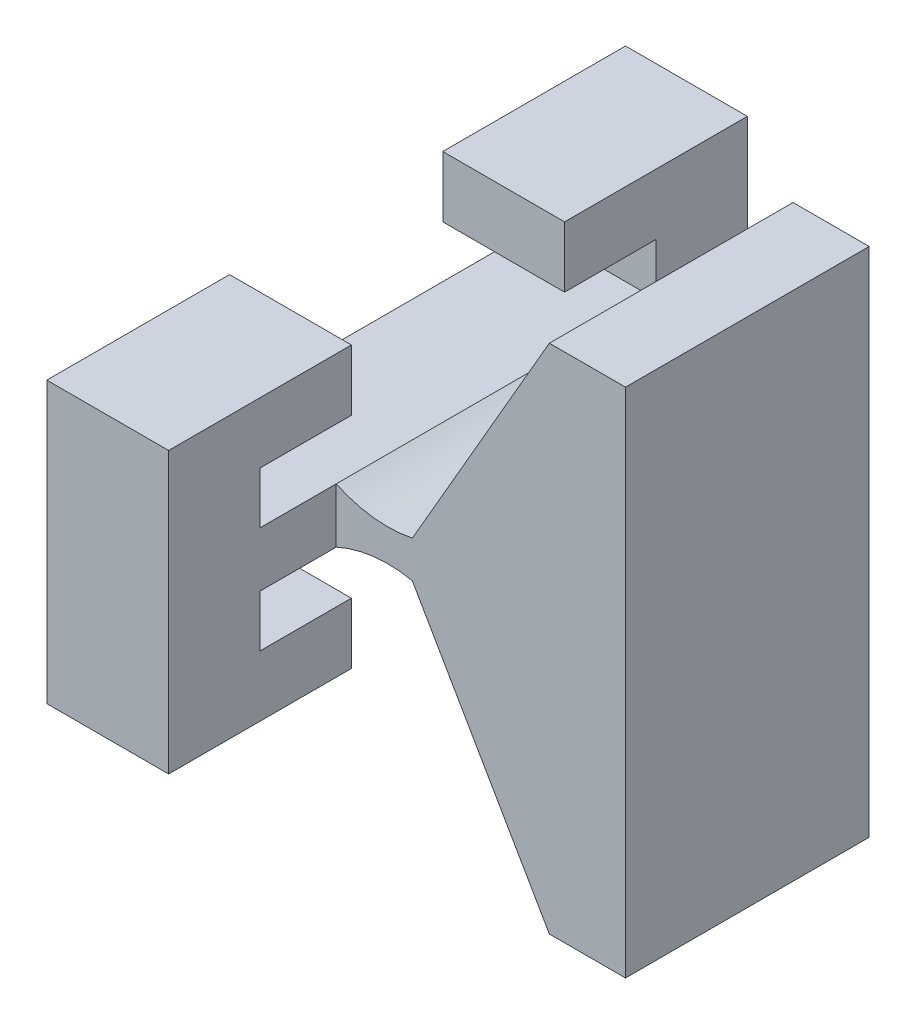
SolidWorks part; units mm, degrees
material "Резина"
ref_plane "Plane1" through (0, 0, 0) normal (0, 0, 1) x (1, 0, 0)
ref_plane "Plane2" through (0, 0, 0) normal (0, 1, 0) x (1, 0, 0)
ref_plane "Plane3" through (0, 0, 0) normal (1, 0, 0) x (0, 0, -1)
sketch "Эскиз2" plane through (0, 0, 0) normal (0, 0, 1) x (1, 0, 0)
  line L0 (0, 0) -> (0, 0.9)
  line L1 (0, 0.9) -> (4, 0.9)
  line L2 (0, 0) -> (34.0426, 0) construction
  line L3 (13.5, 8.4) -> (13.5, -8.4)
  line L4 (11, 8.4) -> (6.5, 0.6058)
  line L5 (11, 8.4) -> (13.5, 8.4)
  line L6 (0, 0) -> (0, -0.9)
  line L7 (0, -0.9) -> (4, -0.9)
  line L8 (11, -8.4) -> (6.5, -0.6058)
  line L9 (11, -8.4) -> (13.5, -8.4)
  arc A0 (6.5, 0.6058) -> (4, 0.9) centre (5.6938, 4.5237) cw
  arc A1 (6.5, -0.6058) -> (4, -0.9) centre (5.6938, -4.5237) ccw
  point P18 (13.5, 0)
  dimension "D1" = 4
  dimension "D2" = 4
  dimension "D3" = 16.8
  dimension "D4" = 2.5
  dimension "D5" = 9
  dimension "D6" = 60
  dimension "D7" = 7
  dimension "D8" = 1.8
  dimension "D9" = 9.5
extrude "Бобышка-Вытянуть1" add sketch "Эскиз2" along normal mid plane 8
sketch "Эскиз3" plane through (0, 0, -4) normal (0, 0, -1) x (-1, 0, 0)
  line L1 (0, -0.9) -> (-4, -0.9)
  line L2 (0, -0.9) -> (0, 0.9)
  line L3 (0, 0.9) -> (-4, 0.9)
  line L4 (-4, -0.9) -> (-4, 0.9)
extrude "Бобышка-Вытянуть2" add sketch "Эскиз3" along normal blind 5.5
mirror "Зеркальное отражение1" about plane through (0, 0, 0) normal (0, 0, 1) of "Бобышка-Вытянуть2"
sketch "Эскиз5" plane through (0, 0.9, 0) normal (0, 1, 0) x (1, 0, 0)
  line L0 (0, 9.5) -> (4, 9.5)
  line L1 (0, 9.5) -> (0, 6.5)
  line L2 (4, 9.5) -> (4, 6.5)
  line L3 (0, 6.5) -> (4, 6.5)
  dimension "D1" = 3
extrude "Бобышка-Вытянуть3" add sketch "Эскиз5" along normal blind 3.7
mirror "Зеркальное отражение2" about plane through (0, 0, 0) normal (0, 0, 1) of "Бобышка-Вытянуть3"
mirror "Зеркальное отражение3" about plane through (0, 0, 0) normal (0, 1, 0) of "Зеркальное отражение2"
sketch "Эскиз7" plane through (0, 0, 6.5) normal (0, 0, -1) x (-1, 0, 0)
  line L0 (0, -4.6) -> (0, 4.6) construction
  line L1 (-4, 4.6) -> (0, 4.6)
  line L2 (-4, 4.6) -> (-4, 2.6)
  line L3 (-4, 2.6) -> (0, 2.6)
  line L4 (0, 4.6) -> (0, 2.6)
  dimension "D1" = 2
extrude "Бобышка-Вытянуть4" add sketch "Эскиз7" along normal blind 3
mirror "Зеркальное отражение4" about plane through (0, 0, 0) normal (0, 0, 1) of "Бобышка-Вытянуть4"
mirror "Зеркальное отражение5" about plane through (0, 0, 0) normal (0, 1, 0) of "Зеркальное отражение4"
